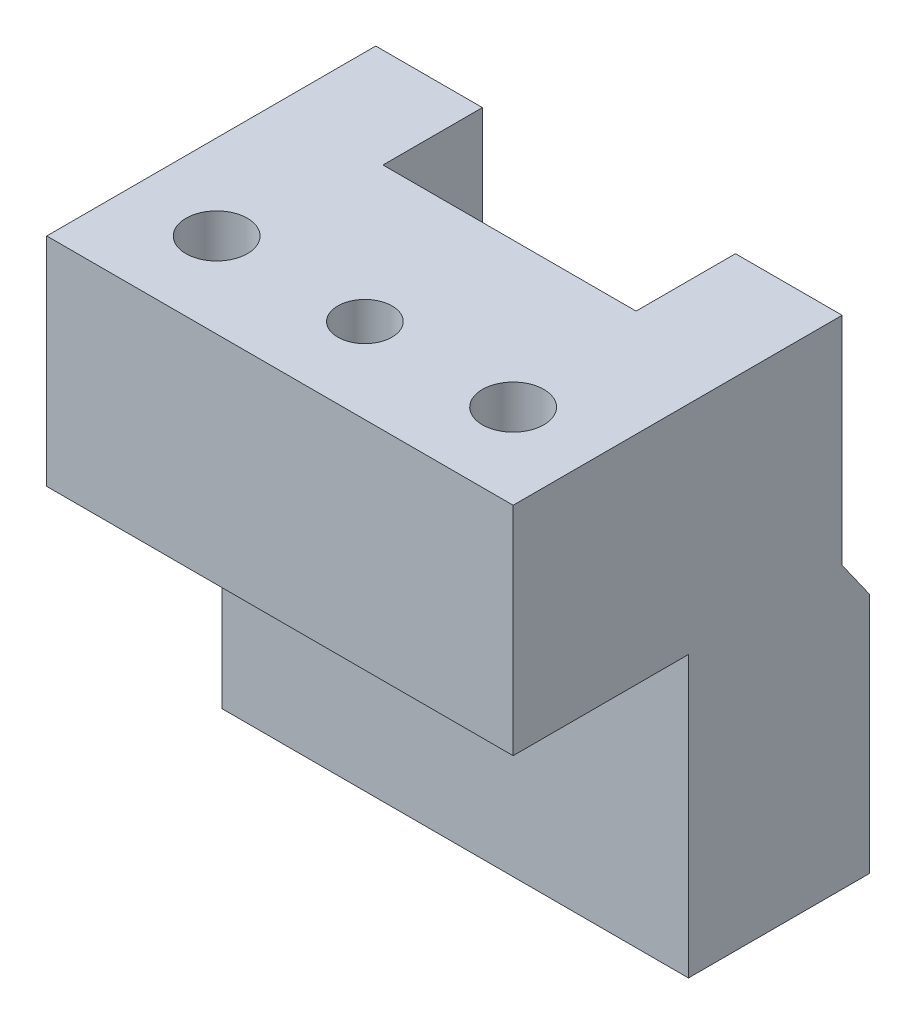
SolidWorks part; units mm, degrees
ref_plane "Front Plane" through (0, 0, 0) normal (0, 0, 1) x (1, 0, 0)
ref_plane "Top Plane" through (0, 0, 0) normal (0, 1, 0) x (1, 0, 0)
ref_plane "Right Plane" through (0, 0, 0) normal (1, 0, 0) x (0, 0, -1)
sketch "Sketch1" plane through (0, 0, 0) normal (0, 1, 0) x (1, 0, 0)
  line L0 (0, 0) -> (25.8, 0)
  line L1 (25.8, 0) -> (25.8, 18.2)
  line L2 (0, 18.2) -> (5.9, 18.2)
  line L3 (19.9, 18.2) -> (19.9, 12.7)
  line L4 (19.9, 12.7) -> (5.9, 12.7)
  line L5 (5.9, 12.7) -> (5.9, 18.2)
  line L6 (19.9, 18.2) -> (25.8, 18.2)
  line L7 (0, 18.2) -> (0, 0)
  line L8 (0, 4.7) -> (4.7, 4.7) construction
  line L9 (4.7, 4.7) -> (12.9, 4.7) construction
  line L10 (12.9, 4.7) -> (21.1, 4.7) construction
  line L11 (21.1, 4.7) -> (25.8, 4.7) construction
  circle A0 centre (4.7, 4.7) radius 1.7
  circle A1 centre (12.9, 4.7) radius 1.5
  circle A2 centre (21.1, 4.7) radius 1.7
  point P17 (12.9, 12.7)
  dimension "D5" = 3
  dimension "D6" = 3.4
  dimension "D1" = 5
  dimension "D4" = 3
  dimension "D2" = 14
  dimension "D3" = 5.5
  dimension "D7" = 3
  dimension "D9" = 8
extrude "Boss-Extrude1" add sketch "Sketch1" along normal blind 12
sketch "Sketch4" plane through (0, 0, 0) normal (0, -1, 0) x (1, 0, 0)
  line L0 (19.9, -18.2) -> (19.9, -12.7) construction
  line L1 (19.9, -12.7) -> (5.9, -12.7) construction
  line L2 (5.9, -12.7) -> (5.9, -18.2) construction
  line L3 (19.9, -18.2) -> (19.9, -12.7)
  line L4 (19.9, -12.7) -> (5.9, -12.7)
  line L5 (5.9, -12.7) -> (5.9, -18.2)
  line L6 (19.9, -18.2) -> (25.8, -18.2)
  line L7 (25.8, -18.2) -> (25.8, -9.7)
  line L8 (25.8, 0) -> (25.8, -18.2) construction
  line L9 (25.8, -9.7) -> (0, -9.7)
  line L10 (0, -18.2) -> (0, 0) construction
  line L11 (0, -9.7) -> (0, -18.2)
  line L12 (0, -18.2) -> (5.9, -18.2)
  dimension "D1" = 3
extrude "Boss-Extrude2" add sketch "Sketch4" along normal blind 15.5
sketch "Sketch5" plane through (0, -15.5, 0) normal (0, -1, 0) x (1, 0, 0)
  line L1 (0, -9.7) -> (0, -18.2) construction
  line L2 (25.8, -18.2) -> (0, -18.2)
  line L3 (25.8, -18.2) -> (25.8, -19.7)
  line L4 (25.8, -19.7) -> (0, -19.7)
  line L5 (0, -18.2) -> (0, -19.7)
  dimension "D1" = 1.5
extrude "Boss-Extrude3" add sketch "Sketch5" against normal blind 3
sketch "Sketch6" plane through (0, 0, -19.7) normal (0, 0, -1) x (-1, 0, 0)
  line L0 (-25.8, -12.5) -> (-25.8, -2.1)
  line L1 (-25.8, 12) -> (-25.8, -12.5) construction
  line L2 (-25.8, -2.1) -> (-15.4, -12.5)
  line L3 (0, -12.5) -> (-25.8, -12.5) construction
  line L4 (-15.4, -12.5) -> (-25.8, -12.5)
  line L5 (0, -12.5) -> (-10.4, -12.5)
  line L6 (-10.4, -12.5) -> (0, -2.1)
  line L7 (0, 12) -> (0, -12.5) construction
  line L8 (0, -2.1) -> (0, -12.5)
  dimension "D1" = 45
  dimension "D2" = 5
extrude "Boss-Extrude4" add sketch "Sketch6" against normal up to surface (1.5 mm away) up to face at (22.85, -0.25, -18.2)
chamfer "Chamfer1" distance 1.5 angle 45 2 edges at (22.85, -5.05, -18.2) (2.95, -5.05, -18.2)
